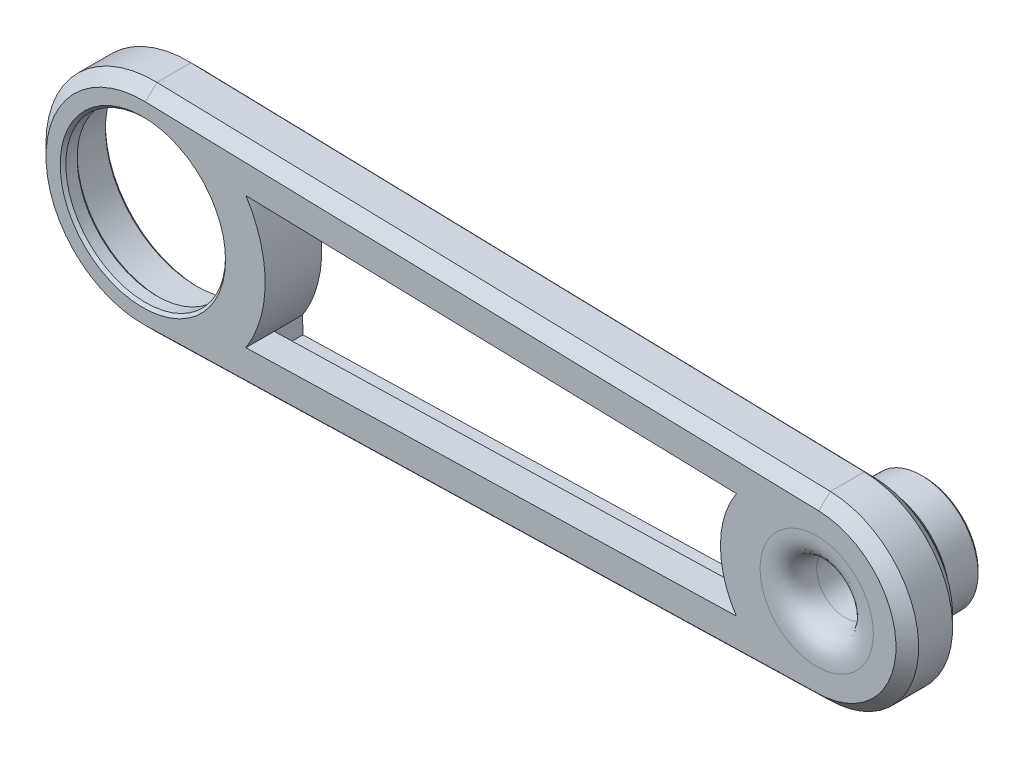
SolidWorks part; units mm, degrees
material "PEI"
ref_plane "前视基准面" through (0, 0, 0) normal (0, 0, 1) x (1, 0, 0)
ref_plane "上视基准面" through (0, 0, 0) normal (0, 1, 0) x (1, 0, 0)
ref_plane "右视基准面" through (0, 0, 0) normal (1, 0, 0) x (0, 0, -1)
other "Configuration Table"
sketch "草图1" plane through (0, 0, 0) normal (0, 0, 1) x (1, 0, 0)
  line L0 (0, 0) -> (119, 0) construction
  line L1 (0.4976, 19.0935) -> (119.4168, 15.9946)
  line L2 (0.4984, -19.0935) -> (119, -16)
  circle A0 centre (119, 0) radius 16
  circle A1 centre (0, 0) radius 16.1
  circle A2 centre (0, 0) radius 19.1
  dimension "D1" = 32.2
  dimension "D3" = 32
  dimension "D2" = 3
  dimension "D4" = 119
extrude "凸台-拉伸1" add sketch "草图1" along normal blind 10
sketch "草图2" plane through (0, 0, 10) normal (0, 0, 1) x (1, 0, 0)
  circle A0 centre (0, 0) radius 16.1 construction
  circle A1 centre (0, 0) radius 16.1
  circle A2 centre (0, 0) radius 14.1
  dimension "D1" = 2
extrude "凸台-拉伸2" add sketch "草图2" against normal blind 3
sketch "草图3" plane through (0, 0, 0) normal (0, 0, -1) x (-1, 0, 0)
  arc A0 (-119.4168, 15.9946) -> (-119, -16) centre (-119, 0) ccw construction
  arc A1 (-119.4168, 15.9946) -> (-119, -16) centre (-119, 0) ccw
  circle A2 centre (-119, 0) radius 10
  dimension "D1" = 20
extrude "凸台-拉伸3" add sketch "草图3" along normal blind 9 contours A2
sketch "草图4" plane through (0, 0, 0) normal (0, 0, -1) x (-1, 0, 0)
  circle A0 centre (-119, 0) radius 10 construction
  circle A1 centre (-119, 0) radius 10
  circle A2 centre (-119, 0) radius 12
  dimension "D1" = 2
extrude "凸台-拉伸4" add sketch "草图4" along normal blind 2
chamfer "倒角1" distance 0.5 angle 45 5 edges at (14.1, 0, 10) (16.1, 0, 0) (14.1, 0, 7) (107, 0, -2) (109, 0, -9)
chamfer "倒角2" distance 2 angle 45 8 edges at (134.9986, -0.2084, 10) (59.9572, 17.544, 10) (-19.1, -0.0004, 10) (59.7492, -17.5467, 10) (134.9986, -0.2084, 0) (59.9572, 17.544, 0) (-19.1, -0.0004, 0) (59.7492, -17.5467, 0)
sketch "草图5" plane through (0, 0, 0) normal (0, 0, -1) x (-1, 0, 0)
  line L0 (-0.3152, 12.0959) -> (-119.2345, 8.9969)
  line L1 (-118.9217, -8.9997) -> (-0.3158, -12.0959)
  line L2 (-0.4455, 17.0942) -> (-119.3647, 13.9952)
  line L3 (-118.9748, -14) -> (-0.4462, -17.0942)
  line L4 (-0.4455, 17.0942) -> (-119.3647, 13.9952)
  line L5 (-118.9748, -14) -> (-0.4462, -17.0942)
  arc A0 (-119.2345, 8.9969) -> (-118.9217, -8.9997) centre (-119, 0) ccw
  arc A1 (-0.3158, -12.0959) -> (-0.3152, 12.0959) centre (0, 0) ccw
  arc A2 (-119.3647, 13.9952) -> (-118.9748, -14) centre (-119, 0) ccw
  arc A3 (-0.4462, -17.0942) -> (-0.4455, 17.0942) centre (0, 0) ccw
  arc A4 (-119.3647, 13.9952) -> (-118.9748, -14) centre (-119, 0) ccw
  arc A5 (-0.4462, -17.0942) -> (-0.4455, 17.0942) centre (0, 0) ccw
  circle A6 centre (-119, 0) radius 12 construction
  circle A7 centre (0, 0) radius 16.6 construction
  circle A30 centre (0, 0) radius 16.6
  circle A31 centre (-119, 0) radius 12
  circle A32 centre (-119, 0) radius 17
  circle A33 centre (0, 0) radius 21.6
  dimension "D1" = 0
  dimension "D2" = 5
  dimension "D3" = 5
extrude "切除-拉伸1" cut sketch "草图5" against normal up to surface (10 mm away) contours A33 L0 A32 L1 up to face at (58.8786, -0.0494, 10)
sketch "草图6" plane through (0, 0, 0) normal (0, 0, -1) x (-1, 0, 0)
  line L0 (-104.814, -9.3679) -> (-18.2024, -11.6289) construction
  line L1 (-18.2019, 11.6298) -> (-104.8171, 9.3727) construction
  line L2 (-104.814, -9.3679) -> (-18.2024, -11.6289)
  line L3 (-18.2019, 11.6298) -> (-104.8171, 9.3727)
  line L4 (-18.28, 14.6288) -> (-104.8953, 12.3716)
  line L5 (-104.8923, -12.3669) -> (-18.2807, -14.6279)
  line L6 (-104.8953, 12.3716) -> (-104.8171, 9.3727)
  line L7 (-104.814, -9.3679) -> (-104.8923, -12.3669)
  line L8 (-18.28, 14.6288) -> (-18.2019, 11.6298)
  line L9 (-18.2024, -11.6289) -> (-18.2807, -14.6279)
  dimension "D1" = 3
extrude "切除-拉伸2" cut sketch "草图6" against normal blind 5
sketch "草图7" plane through (0, 0, -9) normal (0, 0, -1) x (-1, 0, 0)
  circle A0 centre (-119, 0) radius 5
  dimension "D1" = 10
extrude "切除-拉伸3" cut sketch "草图7" against normal up to surface (19 mm away) up to face at (61.6544, 0.0015, 10)
fillet "圆角1" radius 5 1 edges at (124, 0, 10)
equation "\"D4@草图1\"= \"连接杆_后_长度\""
equation "\"连接杆_后_长度\"= 119"
